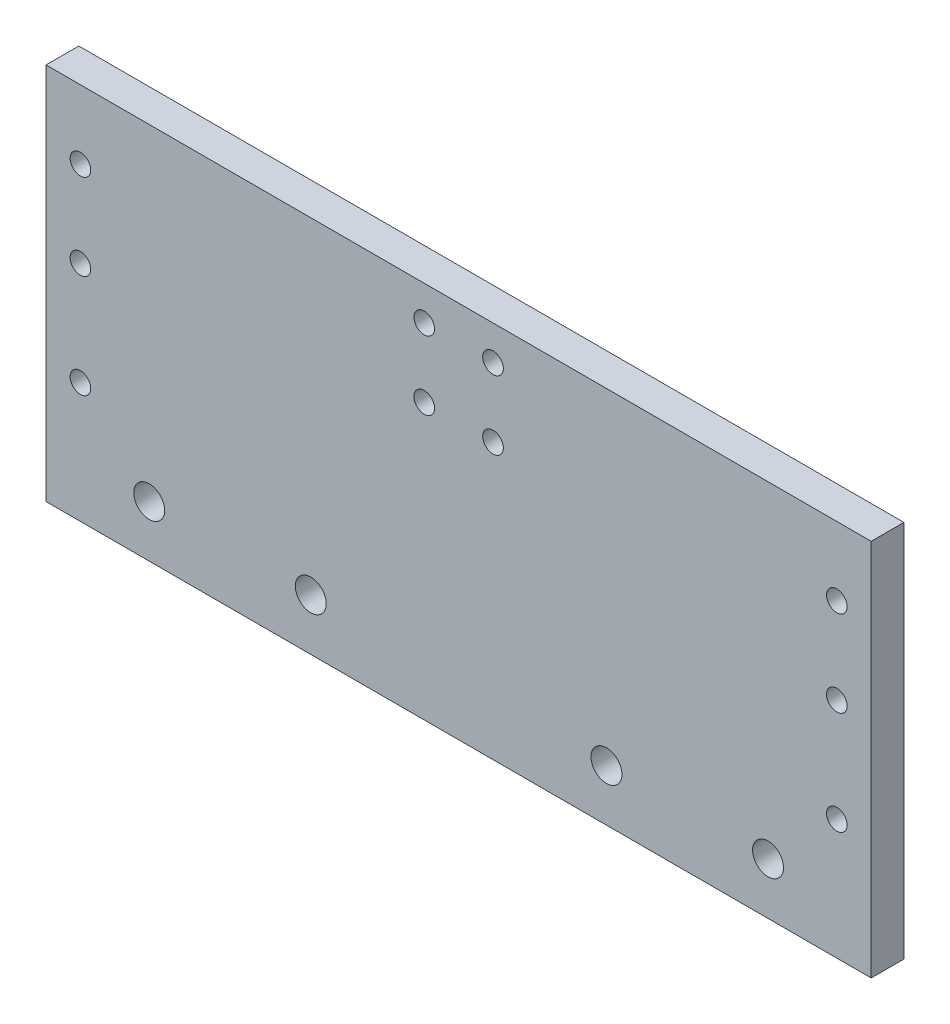
SolidWorks part; units mm, degrees
ref_plane "Front Plane" through (0, 0, 0) normal (0, 0, 1) x (1, 0, 0)
ref_plane "Top Plane" through (0, 0, 0) normal (0, 1, 0) x (1, 0, 0)
ref_plane "Right Plane" through (0, 0, 0) normal (1, 0, 0) x (0, 0, -1)
sketch "Sketch1" plane through (0, 0, 0) normal (0, 0, 1) x (1, 0, 0)
  line L1 (-60, -27.5) -> (60, -27.5)
  line L2 (-60, -27.5) -> (-60, 27.5)
  line L3 (-60, 27.5) -> (60, 27.5)
  line L4 (60, -27.5) -> (60, 27.5)
  line L5 (-60, -27.5) -> (60, 27.5) construction
  line L6 (-60, 27.5) -> (60, -27.5) construction
  point P0 (0, 0)
  dimension "D1" = 120
  dimension "D2" = 55
extrude "Boss-Extrude1" add sketch "Sketch1" along normal blind 4.7625
sketch "Sketch2" plane through (0, 0, 4.7625) normal (0, 0, 1) x (1, 0, 0)
  line L0 (60, 27.5) -> (-60, 27.5) construction
  line L1 (-60, 27.5) -> (-60, -27.5) construction
  line L2 (-60, -27.5) -> (60, -27.5) construction
  line L3 (0, -2.6194) -> (0, 2.6194) construction
  circle A0 centre (-55, 17.5) radius 1.5
  circle A1 centre (-55, 5) radius 1.5
  circle A2 centre (-55, -10) radius 1.5
  circle A6 centre (55, -10) radius 1.5
  circle A7 centre (55, 5) radius 1.5
  circle A8 centre (55, 17.5) radius 1.5
  circle A9 centre (-5, 12.5) radius 1.5
  circle A10 centre (-5, 22.5) radius 1.5
  circle A11 centre (5, 12.5) radius 1.5
  circle A12 centre (5, 22.5) radius 1.5
  circle A13 centre (-45, -20) radius 2.25
  circle A14 centre (-21.5, -20) radius 2.25
  circle A15 centre (45, -20) radius 2.25
  circle A16 centre (21.5, -20) radius 2.25
  dimension "D3" = 3
  dimension "D4" = 3
  dimension "D5" = 3
  dimension "D7" = 37.5
  dimension "D8" = 3
  dimension "D9" = 5
  dimension "D11" = 3
  dimension "D13" = 4.5
  dimension "D14" = 4.5
  dimension "D1" = 10
  dimension "D2" = 12.5
  dimension "D6" = 5
  dimension "D10" = 10
  dimension "D12" = 5
  dimension "D15" = 7.5
  dimension "D16" = 15
  dimension "D17" = 23.5
extrude "Cut-Extrude1" cut sketch "Sketch2" against normal through all
